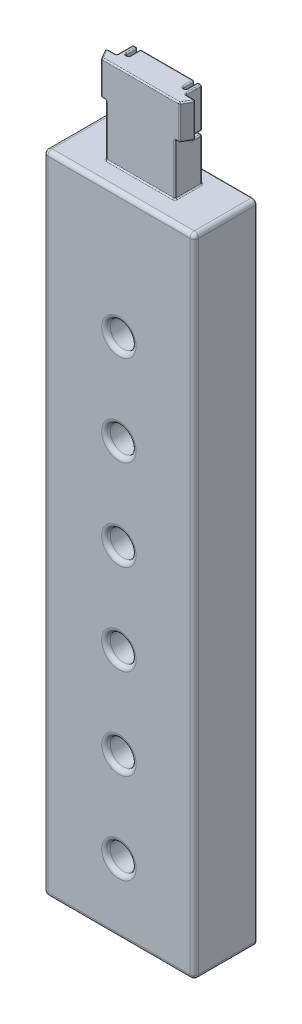
SolidWorks part; units mm, degrees
material "Plain Carbon Steel"
ref_plane "Front Plane" through (0, 0, 0) normal (0, 0, 1) x (1, 0, 0)
ref_plane "Top Plane" through (0, 0, 0) normal (0, 1, 0) x (1, 0, 0)
ref_plane "Right Plane" through (0, 0, 0) normal (1, 0, 0) x (0, 0, -1)
sketch "Sketch1" plane through (0, 0, 0) normal (0, 0, 1) x (1, 0, 0)
  circle A3 centre (0, 0) radius 18
  dimension "D1" = 36
extrude "Boss-Extrude1" add sketch "Sketch1" along normal blind 19
sketch "Sketch3" plane through (0, 0, 19) normal (0, 0, 1) x (1, 0, 0)
  line L0 (0, 0) -> (0, -98.6978) construction
  line L3 (-17.5, -4.2131) -> (-17.5, -192)
  line L4 (-17.5, -192) -> (17.5, -192)
  line L5 (17.5, -4.2131) -> (17.5, -192)
  arc A1 (-17.5, -4.2131) -> (17.5, -4.2131) centre (0, 0) ccw
  circle A2 centre (0, 0) radius 18 construction
  dimension "D1" = 35
  dimension "D2" = 192
extrude "Boss-Extrude2" add sketch "Sketch3" against normal blind 14.5 contours L5 L4 L3 A1
sketch "Sketch4" plane through (0, 0, 4.5) normal (0, 0, -1) x (-1, 0, 0)
  line L0 (0, 0) -> (0, -224.52) construction
  circle A0 centre (0, -71) radius 3
  circle A1 centre (0, -92) radius 3
  circle A2 centre (0, -113) radius 3
  circle A3 centre (0, -134) radius 3
  circle A4 centre (0, -155) radius 3
  circle A5 centre (0, -176) radius 3
  dimension "D1" = 6
  dimension "71" = 71
  dimension "D3" = 6
extrude "Cut-Extrude2" cut sketch "Sketch4" against normal through all both and the other way through all
sketch "Sketch5" plane through (0, 0, 0) normal (0, 0, -1) x (-1, 0, 0)
  line L0 (0, 0) -> (0, 18) construction
  line L1 (0, 0) -> (-9, 15.5885) construction
  circle A0 centre (0, 0) radius 12 construction
  circle A1 centre (-6, 10.3923) radius 2.25
  circle A2 centre (0, 0) radius 18 construction
  circle A3 centre (12, 0) radius 2.25
  circle A4 centre (-6, -10.3923) radius 2.25
  point P17 (0, 0)
  dimension "D1" = 24
  dimension "D3" = 4.5
  dimension "D2" = 30
  dimension "D4" = 3
extrude "Cut-Extrude3" cut sketch "Sketch5" against normal blind 3
sketch "Sketch6" plane through (0, 0, 0) normal (0, 0, -1) x (-1, 0, 0)
  circle A0 centre (0, 0) radius 13.5 construction
  circle A1 centre (0, 13.5) radius 1.65
  circle A2 centre (11.6913, 6.75) radius 1.65
  circle A3 centre (11.6913, -6.75) radius 1.65
  circle A4 centre (0, -13.5) radius 1.65
  circle A5 centre (-11.6913, -6.75) radius 1.65
  circle A6 centre (-11.6913, 6.75) radius 1.65
  point P17 (0, 0)
  dimension "D1" = 27
  dimension "D2" = 3.3
  dimension "D3" = 6
extrude "Cut-Extrude4" cut sketch "Sketch6" against normal through all
sketch "Sketch7" plane through (0, 0, 19) normal (0, 0, 1) x (1, 0, 0)
  circle A0 centre (0, 13.5) radius 2.95
  circle A1 centre (11.6913, 6.75) radius 2.95
  circle A2 centre (11.6913, -6.75) radius 2.95
  circle A3 centre (0, -13.5) radius 2.95
  circle A4 centre (-11.6913, -6.75) radius 2.95
  circle A5 centre (-11.6913, 6.75) radius 2.95
  dimension "D1" = 5.9
  dimension "D2" = 5.9
  dimension "D3" = 5.9
  dimension "D4" = 5.9
  dimension "D5" = 5.9
  dimension "D6" = 5.9
extrude "Cut-Extrude5" cut sketch "Sketch7" against normal offset from surface (17 mm away) 2 up to face at (-1.65, 13.5, 0)
sketch "Sketch8" plane through (0, 0, 4.5) normal (0, 0, -1) x (-1, 0, 0)
  line L0 (0, -192) -> (0, 0) construction
  line L1 (17.5, -192) -> (-17.5, -192) construction
  line L2 (-17.5, -192) -> (17.5, -192)
  line L3 (17.5, -192) -> (17.5, -42)
  line L4 (17.5, -4.2131) -> (17.5, -192) construction
  line L5 (17.5, -42) -> (8, -42)
  line L6 (8, -42) -> (8, -22)
  line L7 (8, -22) -> (-8, -22)
  line L8 (-8, -22) -> (-8, -42)
  line L9 (-8, -42) -> (-17.5, -42)
  line L10 (-17.5, -4.2131) -> (-17.5, -192) construction
  line L11 (-17.5, -42) -> (-17.5, -192)
  dimension "D1" = 150
  dimension "D2" = 16
  dimension "D3" = 170
extrude "Cut-Extrude7" cut sketch "Sketch8" against normal through all both and the other way through all flip side to cut
sketch "Sketch9" plane through (0, 0, 19) normal (0, 0, 1) x (1, 0, 0)
  line L1 (-8, -22) -> (8, -22)
  line L2 (-8, -22) -> (-8, -42)
  line L3 (-8, -42) -> (8, -42)
  line L4 (8, -22) -> (8, -42)
extrude "Cut-Extrude8" cut sketch "Sketch9" against normal blind 5 and the other way through all
sketch "Sketch18" plane through (0, 0, 4.5) normal (0, 0, -1) x (-1, 0, 0)
  line L1 (-8, -22) -> (8, -22)
  line L2 (-8, -22) -> (-8, -42)
  line L3 (-8, -42) -> (8, -42)
  line L4 (8, -22) -> (8, -42)
  line L5 (-8, -22) -> (8, -42) construction
  line L6 (-8, -42) -> (8, -22) construction
  point P4 (0, -32)
extrude "Cut-Extrude13" cut sketch "Sketch18" against normal blind 3.2
sketch "Sketch10" plane through (0, -22, 0) normal (0, 1, 0) x (1, 0, 0)
  line L1 (8, -14) -> (9.0566, -14)
  line L2 (9.0566, -14) -> (10.5, -11.5)
  line L3 (10.5, -11.5) -> (8, -11.5)
  line L9 (8, -14) -> (-8, -14) construction
  line L10 (8, -11.5) -> (8, -14)
  dimension "D1" = 2.5
  dimension "D2" = 60
  dimension "D4" = 2.5
extrude "Boss-Extrude3" add sketch "Sketch10" against normal blind 8
sketch "Sketch16" plane through (0, -22, 0) normal (0, 1, 0) x (1, 0, 0)
  line L0 (0, -4.5) -> (0, -19) construction
  line L1 (8, -4.5) -> (-8, -4.5) construction
  line L2 (-17.5, -19) -> (17.5, -19) construction
  line L4 (6.25, -4.5) -> (7, -4.5)
  line L5 (6.25, -4.5) -> (6.25, -10.5)
  line L6 (6.25, -10.5) -> (7, -10.5)
  line L7 (7, -4.5) -> (7, -10.5)
  dimension "D1" = 6
  dimension "D2" = 0.75
  dimension "D3" = 6.25
extrude "Cut-Extrude11" cut sketch "Sketch16" against normal offset from surface (10 mm away) 2 up to face at (8.8892, -30, 12.75) offset beyond the face yes
sketch "Sketch17" plane through (8, 0, 0) normal (1, 0, 0) x (0, 0, -1)
  line L0 (-4.5, -42) -> (-4.5, -22) construction
  line L1 (-10.5, -31.25) -> (-4.5, -31.25)
  line L2 (-10.5, -31.25) -> (-10.5, -32)
  line L3 (-10.5, -32) -> (-4.5, -32)
  line L4 (-4.5, -31.25) -> (-4.5, -32)
  line L6 (-10.5, -32) -> (-10.5, -22) construction
  point P4 (-10.5, -31.625)
  dimension "D1" = 0.75
  dimension "D3" = 0
extrude "Cut-Extrude12" cut sketch "Sketch17" against normal up to surface (1.75 mm away) up to face at (6.25, -27, 9.1)
ref_plane "Plane1" through (0, 0, 0) normal (-1, 0, 0) x (0, 0, 1)
mirror "Mirror1" about plane through (0, 0, 0) normal (-1, 0, 0) of "Cut-Extrude12", "Cut-Extrude11", "Boss-Extrude3"
fillet "Fillet2" radius 0.3 70 edges at (0, -42, 4.5) (0, -42, 14) (8.5283, -30, 14) (9.25, -30, 11.5) (10.5, -26, 11.5) (-8, -42, 10.85) (-8, -36, 14) (9.25, -22, 11.5) (9.7783, -22, 12.75) (0, -22, 14) (-9.7783, -22, 12.75) (-9.25, -22, 11.5) (8, -42, 10.85) (8, -36, 14) (8, -30, 12.75) (-9.25, -30, 11.5) (-9.7783, -30, 12.75) (-8.5283, -30, 14) (-8, -30, 12.75) (-9.0566, -26, 14) (9.0566, -26, 14) (-10.5, -26, 11.5) (-8, -26, 11.5) (-8, -22, 9.6) (8, -22, 9.6) (8, -26, 11.5) (9.7783, -30, 12.75) (-8, -32, 9.1) (-6.25, -22, 9.1) (6.25, -22, 9.1) (6.625, -22, 10.5) (7, -22, 9.1) (-7, -22, 9.1) (-6.625, -22, 10.5) (8, -32, 9.1) (-6.25, -32, 9.1) (-7.125, -32, 10.5) (7.125, -32, 10.5) (0, -42, 7.7) (-17.5, -117, 4.5) (0, -192, 4.5) (17.5, -117, 4.5) (8, -37, 7.7) (8, -26.625, 7.7) (8, -31.25, 9.1) (8, -31.625, 10.5) (-8, -31.25, 9.1) (-8, -26.625, 7.7) (-8, -37, 7.7) (-8, -31.625, 10.5) (-7.125, -32, 7.7) (-7, -26.625, 10.5) (-6.25, -27, 7.7) (-6.25, -27, 10.5) (0, -22, 7.7) (7.125, -32, 7.7) (6.25, -27, 7.7) (6.25, -32, 9.1) (6.25, -27, 10.5) (7, -26.625, 10.5) (-7.5, -31.25, 10.5) (-7, -31.25, 9.1) (-7.5, -22, 7.7) (-7.5, -31.25, 7.7) (-7, -26.625, 7.7) (7, -31.25, 9.1) (7.5, -31.25, 10.5) (7.5, -22, 7.7) (7, -26.625, 7.7) (7.5, -31.25, 7.7)
fillet "Fillet1" radius 1 24 edges at (-17.5, -192, 11.9) (17.5, -192, 11.9) (-17.5, -117, 19) (0, -192, 19) (17.5, -117, 19) (3, -176, 4.5) (3, -155, 4.5) (3, -134, 4.5) (3, -113, 4.5) (3, -92, 4.5) (3, -71, 4.5) (-3, -176, 19) (-3, -155, 19) (-3, -134, 19) (-3, -113, 19) (-3, -92, 19) (-3, -71, 19) (-17.5, -42, 11.9) (17.5, -42, 11.9) (0, -42, 19) (-17.4121, -42.0879, 4.5879) (-17.4121, -191.9121, 4.5879) (17.4121, -191.9121, 4.5879) (17.4121, -42.0879, 4.5879)
